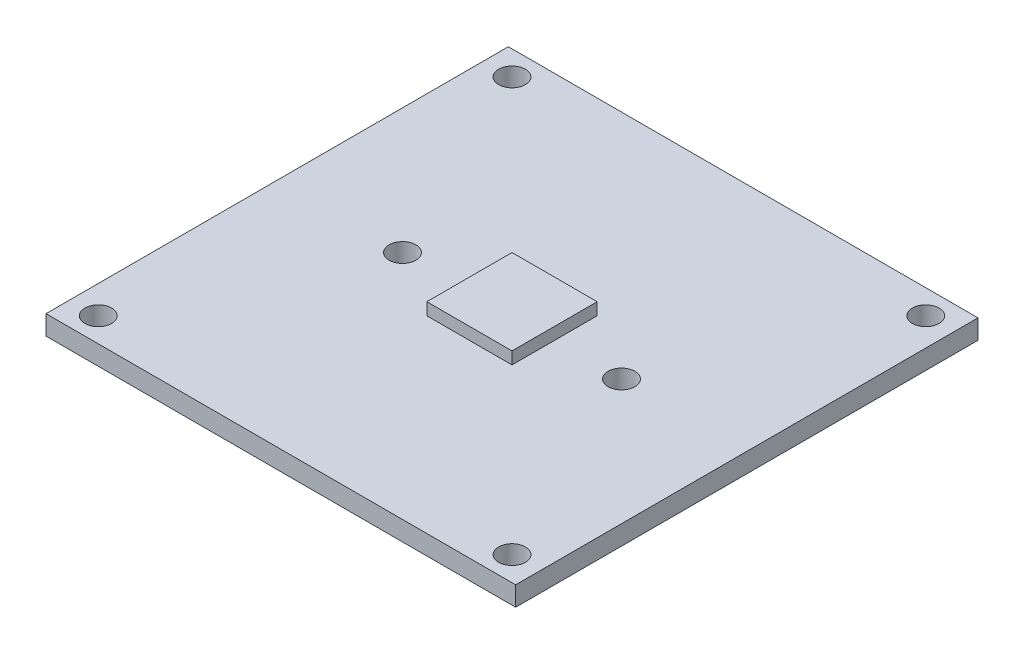
SolidWorks part; units mm, degrees
material "FR4_stuffedProtoboard"
ref_plane "Front Plane" through (0, 0, 0) normal (0, 0, 1) x (1, 0, 0)
ref_plane "Top Plane" through (0, 0, 0) normal (0, 1, 0) x (1, 0, 0)
ref_plane "Right Plane" through (0, 0, 0) normal (1, 0, 0) x (0, 0, -1)
sketch "Sketch1" plane through (0, 0, 0) normal (0, 1, 0) x (1, 0, 0)
  line L1 (-19.3, -19) -> (19.3, -19)
  line L2 (-19.3, -19) -> (-19.3, 19)
  line L3 (-19.3, 19) -> (19.3, 19)
  line L4 (19.3, -19) -> (19.3, 19)
  line L5 (-19.3, -19) -> (19.3, 19) construction
  line L6 (-19.3, 19) -> (19.3, -19) construction
  line L16 (-7.9, 0) -> (7.9, 0) construction
  line L17 (15.9, 17) -> (-15.9, 17) construction
  line L18 (17, 15.9) -> (17, -15.9) construction
  line L23 (3.5, 3.5) -> (-3.5, 3.5)
  line L24 (3.5, 3.5) -> (3.5, -3.5)
  line L29 (3.5, -3.5) -> (-3.5, -3.5)
  line L30 (-3.5, 3.5) -> (-3.5, -3.5)
  line L31 (3.5, 3.5) -> (-3.5, -3.5) construction
  line L32 (3.5, -3.5) -> (-3.5, 3.5) construction
  circle A8 centre (-17, 17) radius 1.1
  circle A9 centre (17, 17) radius 1.1
  circle A10 centre (17, -17) radius 1.1
  circle A11 centre (-17, -17) radius 1.1
  circle A13 centre (9, 0) radius 1.1
  circle A14 centre (-9, 0) radius 1.1
  point P0 (15.9, 17)
  point P5 (15.9, -17)
  point P7 (-15.9, 17)
  point P10 (0, 0)
  point P17 (17, 18.1)
  point P18 (18.1, 17)
  point P19 (17, -18.1)
  point P20 (17, 15.9)
  point P24 (17, -15.9)
  point P32 (9, -1.1)
  point P35 (10.1, 0)
  point P37 (7.9, 0)
  point P38 (-7.9, 0)
  point P39 (-10.1, 0)
  point P40 (9, 1.1)
  point P41 (-28.5607, 5.9244)
  point P43 (0, 0)
  point P44 (0, 17)
  point P45 (17, 0)
  point P46 (0, 0)
  dimension "D3" = 31.8
  dimension "D6" = 17.9
  dimension "D7" = 2.2
  dimension "D10" = 2.2
  dimension "D1" = 38
  dimension "D2" = 38.6
  dimension "D4" = 7
  dimension "D5" = 15.8
  dimension "D11" = 31.8
extrude "Camera Board Base" add sketch "Sketch1" against normal blind 1.6 contours L1 L4 L3 L2 A9 A8 A10 A11 | L23 L30 L29 L24 region at (-18.7583, 0, 0) region at (0, 0, 0)
extrude "Sensor" add sketch "Sketch1<5>" along normal blind 1 contours L23 L30 L29 L24 region at (0, 0, 0)
sketch "Sketch1<5>" plane through (0, 0, 0) normal (0, 1, 0) x (1, 0, 0) same geometry as "Sketch1"
sketch "Footprint" plane through (0, 0, 0) normal (0, 1, 0) x (1, 0, 0)
  line L0 (-7.3, 2.3) -> (-8.8075, 2.3)
  line L1 (-7.3, 7.7) -> (7.3, 7.7)
  line L2 (-7.3, 7.7) -> (-7.3, -7.7)
  line L3 (-7.3, -7.7) -> (7.3, -7.7)
  line L4 (7.3, 7.7) -> (7.3, -7.7)
  line L5 (-7.3, 7.7) -> (7.3, -7.7) construction
  line L6 (-7.3, -7.7) -> (7.3, 7.7) construction
  line L7 (-6.3, 6.7) -> (6.3, 6.7)
  line L8 (-6.3, 6.7) -> (-6.3, -6.7)
  line L9 (-6.3, -6.7) -> (6.3, -6.7)
  line L10 (6.3, 6.7) -> (6.3, -6.7)
  line L11 (-6.3, 6.7) -> (6.3, -6.7) construction
  line L12 (-6.3, -6.7) -> (6.3, 6.7) construction
  line L13 (-8.8075, -2.3) -> (-7.3, -2.3)
  line L14 (7.3, 2.3) -> (8.8075, 2.3)
  line L15 (7.3, -2.3) -> (8.8075, -2.3)
  line L16 (-11.1, 0) -> (11.1, 0) construction
  circle A0 centre (-9, 0) radius 1
  circle A1 centre (-9, 0) radius 1.1 construction
  circle A2 centre (9, 0) radius 1
  arc A3 (8.8075, 2.3) -> (8.8075, -2.3) centre (8.8, 0) cw
  arc A4 (-8.8075, 2.3) -> (-8.8075, -2.3) centre (-8.8, 0) ccw
  point P0 (0, 0)
  point P7 (0, 0)
  point P29 (0, 0)
  point P30 (-23.1319, 3.9024)
  point P31 (-25.4275, 5.0834)
  point P32 (0, 0)
  point P33 (0, 0)
  point P34 (-42.5003, 16.4125)
  point P35 (0, 0)
  point P36 (-12.1269, 2.5502)
  point P37 (0, 0)
  point P38 (-49.4238, 8.8701)
  dimension "D7" = 2
  dimension "D1" = 14.6
  dimension "D2" = 15.4
  dimension "D3" = 1
  dimension "D4" = 1
  dimension "D5" = 1
  dimension "D6" = 1
  dimension "D8" = 18
  dimension "D9" = 4.6
  dimension "D10" = 22.2
  dimension "D11" = 3.8
